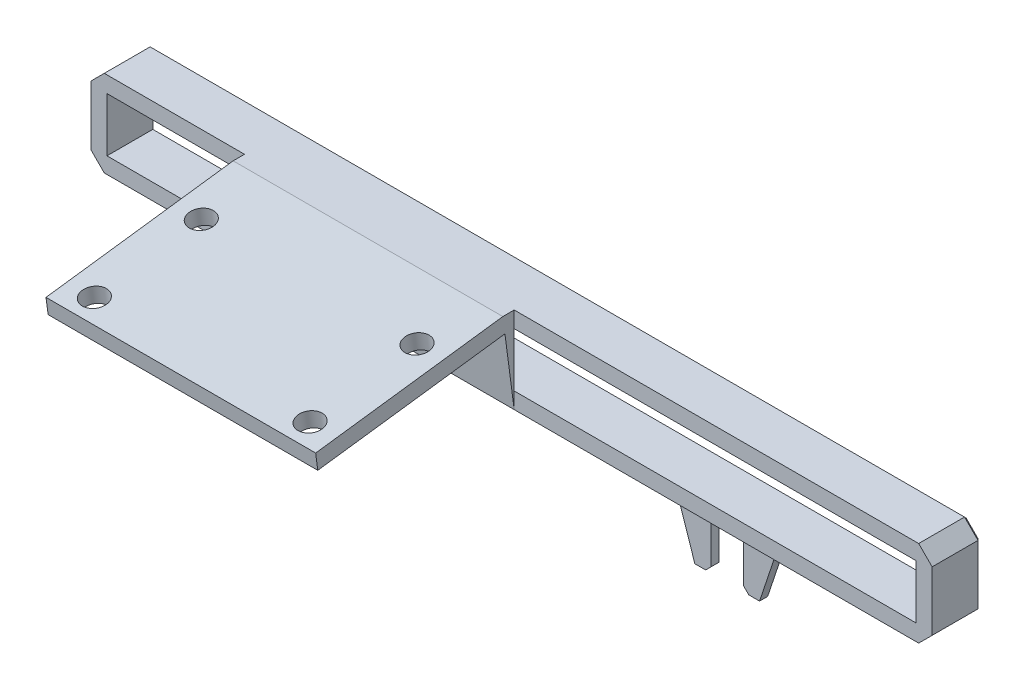
SolidWorks part; units mm, degrees
ref_plane "Top Plane" through (0, 0, 0) normal (0, 0, 1) x (1, 0, 0)
ref_plane "Front Plane" through (0, 0, 0) normal (0, 1, 0) x (1, 0, 0)
ref_plane "Right Plane" through (0, 0, 0) normal (1, 0, 0) x (0, 0, -1)
sketch "Sketch1" plane through (0, 0, 0) normal (0, 0, 1) x (1, 0, 0)
  line L1 (0, 0) -> (156, 0)
  line L2 (0, 0) -> (0, 16)
  line L3 (0, 16) -> (156, 16)
  line L4 (156, 0) -> (156, 16)
  dimension "D1" = 156
  dimension "D2" = 16
extrude "Boss-Extrude1" add sketch "Sketch1" along normal blind 9
sketch "Sketch2" plane through (0, 0, 9) normal (0, 0, 1) x (1, 0, 0)
  line L14 (153, 3) -> (153, 13)
  line L15 (3, 3) -> (153, 3)
  line L16 (3, 13) -> (3, 3)
  line L17 (153, 13) -> (3, 13)
  line L18 (153, 3) -> (153, 13)
  line L19 (3, 3) -> (153, 3)
  line L20 (3, 13) -> (3, 3)
  line L21 (153, 13) -> (3, 13)
  dimension "D1" = 3
extrude "Cut-Extrude1" cut sketch "Sketch2" against normal blind 9
sketch "Sketch4" plane through (156, 0, 0) normal (1, 0, 0) x (0, 0, -1)
  line L0 (-9, 16) -> (-11.1064, 16)
  line L1 (-11.1064, 16) -> (-9, 0)
  line L2 (-9, 0) -> (-9, 16)
  dimension "D1" = 7.5
extrude "Boss-Extrude2" add sketch "Sketch4" along normal blind 50 from offset 127.5 offset against normal yes
sketch "Sketch5" plane through (0, -1.1647, 8.8467) normal (0, -0.1305, 0.9914) x (1, 0, 0)
  line L0 (78.5, 17.3128) -> (78.5, 1.1747) construction
  line L1 (28.5, 17.3128) -> (78.5, 17.3128)
  line L2 (28.5, 17.3128) -> (28.5, 14.3128)
  line L3 (28.5, 14.3128) -> (78.5, 14.3128)
  line L4 (78.5, 17.3128) -> (78.5, 14.3128)
  line L6 (78.5, 17.3128) -> (28.5, 17.3128) construction
  line L7 (28.5, 17.3128) -> (28.5, 1.1747) construction
  dimension "D1" = 3
extrude "Boss-Extrude3" add sketch "Sketch5" along normal blind 35
sketch "Sketch6" plane through (0, 17.1647, 2.2598) normal (0, 0.9914, 0.1305) x (1, 0, 0)
  line L0 (78.5, -8.923) -> (28.5, -8.923) construction
  line L1 (33.5, -19.923) -> (73.5, -19.923)
  line L2 (33.5, -19.923) -> (33.5, -39.923)
  line L3 (33.5, -39.923) -> (73.5, -39.923)
  line L4 (73.5, -19.923) -> (73.5, -39.923)
  line L5 (28.5, -43.923) -> (28.5, -8.923) construction
  dimension "D1" = 40
  dimension "D2" = 20
  dimension "D3" = 11
  dimension "D4" = 5
hole_wizard "M4 Clearance Hole1" positions "Sketch7" profile "Sketch8" hole size "M4" standard "DIN" end condition through all
sketch "Sketch7" plane through (0, 17.1647, 2.2598) normal (0, 0.9914, 0.1305) x (1, 0, 0)
  point P0 (33.5, -19.923)
  point P3 (73.5, -19.923)
  point P6 (73.5, -39.923)
  point P9 (33.5, -39.923)
sketch "Sketch8" plane through (33.5, 14.5642, 22.0123) normal (1, 0, 0) x (0, -0.1305, 0.9914)
  line L0 (0, 0) -> (0, 17.3128)
  line L1 (0, 17.3128) -> (2.25, 17.3128)
  line L2 (2.25, 17.3128) -> (2.25, 0)
  line L5 (2.25, 0) -> (0, 0)
  line L11 (0, -6.35) -> (0, 107.95) construction
  dimension "Thru Hole Dia." = 4.5
  dimension "Thru Hole Depth" = 17.3128
sketch "Sketch10" plane through (0, 0, 0) normal (0, -1, 0) x (1, 0, 0)
  line L0 (0, 0) -> (156, 0) construction
  line L1 (105, 2) -> (117, 2)
  line L2 (105, 2) -> (105, 0)
  line L3 (105, 0) -> (117, 0)
  line L4 (117, 2) -> (117, 0)
  line L5 (156, 9) -> (156, 0) construction
  dimension "D1" = 2
  dimension "D2" = 12
  dimension "D3" = 39
extrude "Boss-Extrude4" add sketch "Sketch10" along normal blind 15
sketch "Sketch11" plane through (0, 0, 0) normal (0, 0, -1) x (-1, 0, 0)
  line L0 (-105, -15) -> (-117, -15) construction
  line L1 (-114, -15) -> (-108, -15)
  line L2 (-114, -15) -> (-114, -4)
  line L3 (-114, -4) -> (-108, -4)
  line L4 (-108, -15) -> (-108, -4)
  line L5 (0, 0) -> (-105, 0) construction
  line L6 (-105, -15) -> (-105, 0) construction
  dimension "D1" = 6
  dimension "D2" = 4
  dimension "D3" = 3
extrude "Cut-Extrude2" cut sketch "Sketch11" against normal blind 15
chamfer "Chamfer1" distance 5 distance2 15 2 edges at (117, 0, 1) (105, 0, 1) first distance on face at (86.3, 0, 4)
chamfer "Chamfer2" distance 1 angle 45 2 edges at (108, -15, 1) (114, -15, 1)
chamfer "Chamfer3" distance 2.5 angle 45 4 edges at (0, 0, 4.5) (0, 16, 4.5) (156, 16, 4.5) (156, 0, 4.5)
chamfer "Chamfer4" distance 2 angle 45 1 edges at (111, 0, 2)
chamfer "Chamfer5" distance 0.5 angle 45 22 edges at (3, 8, 0) (78, 13, 0) (153, 8, 0) (78, 3, 0) (102.5, -7.5, 0) (106, -15, 0) (107.5, -14.5, 0) (108, -9, 0) (111, -4, 0) (114, -9, 0) (114.5, -14.5, 0) (116, -15, 0) (119.5, -7.5, 0) (137.75, 0, 0) (154.75, 1.25, 0) (156, 8, 0) (154.75, 14.75, 0) (78, 16, 0) (1.25, 14.75, 0) (0, 8, 0) (1.25, 1.25, 0) (51.25, 0, 0)
ref_plane "Plane1" through (53.5, 0, 0) normal (-1, 0, 0) x (0, 0, 1)
ref_plane "Plane2" through (78, 0, 0) normal (-1, 0, 0) x (0, 0, 1)
